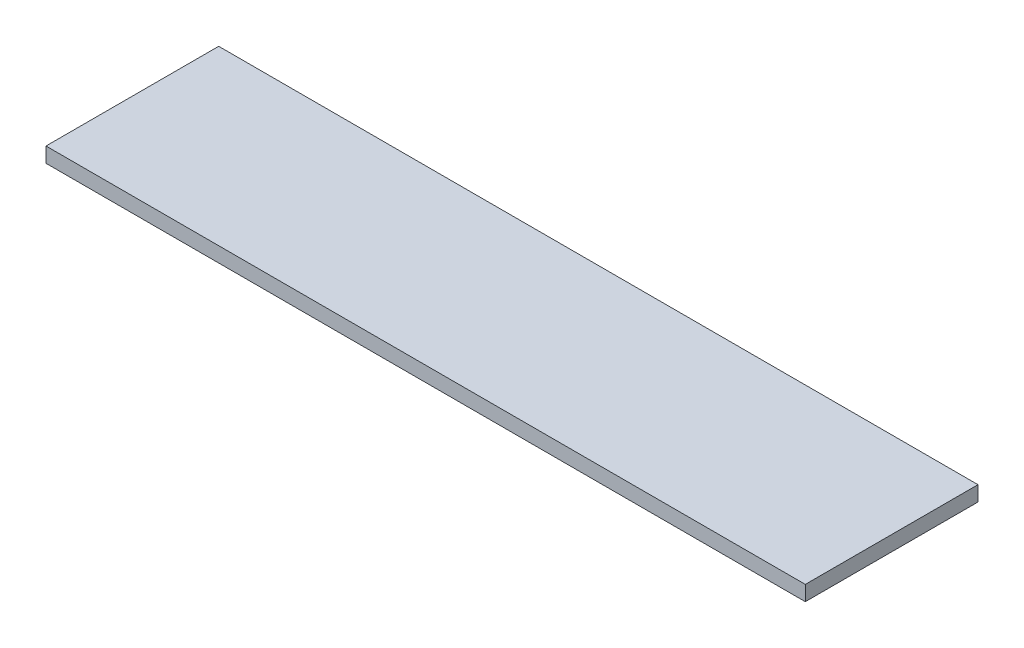
SolidWorks part; units mm, degrees
ref_plane "Front" through (0, 0, 0) normal (0, 0, 1) x (1, 0, 0)
ref_plane "Top" through (0, 0, 0) normal (0, 1, 0) x (1, 0, 0)
ref_plane "Right" through (0, 0, 0) normal (1, 0, 0) x (0, 0, -1)
sketch "Sketch1" plane through (0, 0, 0) normal (0, 1, 0) x (1, 0, 0)
  line L1 (-2413, 584.2) -> (2413, 584.2)
  line L2 (-2413, 584.2) -> (-2413, -584.2)
  line L3 (-2413, -584.2) -> (2413, -584.2)
  line L4 (2413, 584.2) -> (2413, -584.2)
  line L5 (-2413, 584.2) -> (2413, -584.2) construction
  line L6 (-2413, -584.2) -> (2413, 584.2) construction
  point P0 (0, 0)
  dimension "D1" = 4826
  dimension "D2" = 1168.4
extrude "Boss-Extrude1" add sketch "Sketch1" along normal blind 101.6
sketch "Sketch2" plane through (0, 101.6, 0) normal (0, 1, 0) x (1, 0, 0)
  line L0 (2413, -584.2) -> (2413, 584.2) construction
  line L1 (-2413, 584.2) -> (2413, 584.2)
  line L2 (-2413, 584.2) -> (-2413, 0)
  line L3 (-2413, 0) -> (2413, 0)
  line L4 (2413, 584.2) -> (2413, 0)
  line L5 (-2413, -584.2) -> (2413, -584.2) construction
  dimension "D1" = 584.2
extrude "Cut-Extrude1" [suppressed] cut sketch "Sketch2" against normal through all
sketch "Sketch4" plane through (0, 101.6, 0) normal (0, 1, 0) x (1, 0, 0)
  line L0 (2413, 584.2) -> (-2413, 584.2) construction
  line L1 (-2413, -584.2) -> (-2724.15, -584.2)
  line L2 (-2413, -584.2) -> (-2413, 584.2)
  line L3 (-2413, 584.2) -> (-2724.15, 584.2)
  line L4 (-2724.15, -584.2) -> (-2724.15, 584.2)
  line L5 (2413, -584.2) -> (2413, 584.2) construction
  dimension "D1" = 5137.15
extrude "Boss-Extrude2" add sketch "Sketch4" against normal up to surface (101.6 mm away) up to face at (0, 0, 0)
